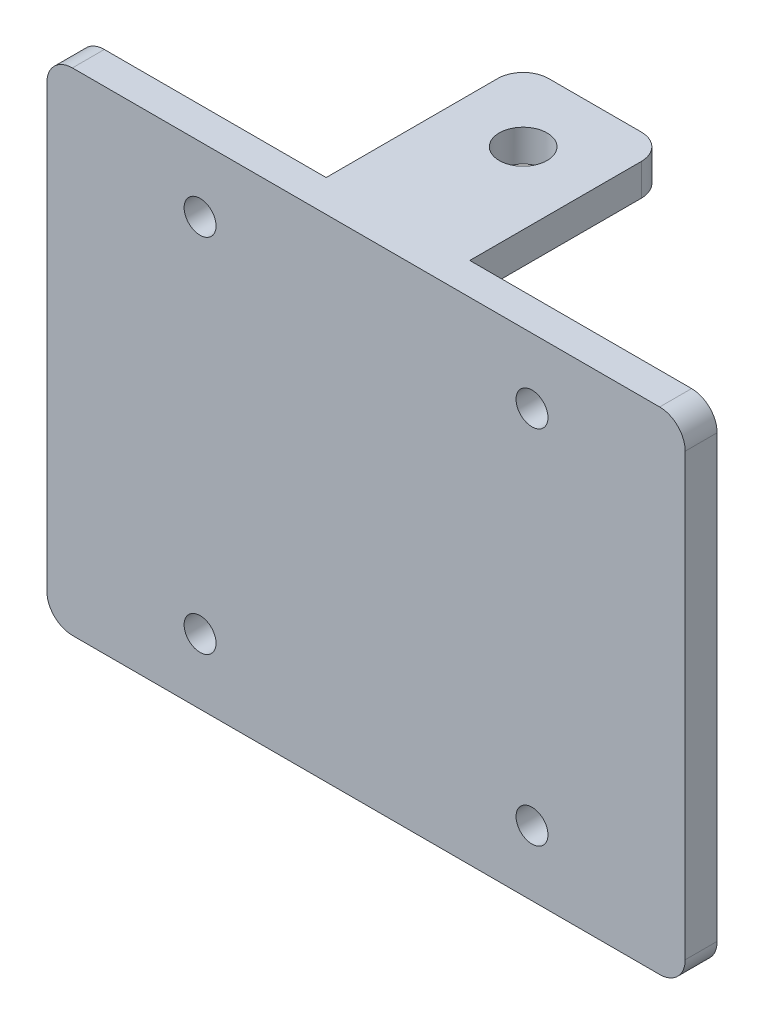
SolidWorks part; units mm, degrees
material "6061 Alloy"
ref_plane "Front Plane" through (0, 0, 0) normal (0, 0, 1) x (1, 0, 0)
ref_plane "Top Plane" through (0, 0, 0) normal (0, 1, 0) x (1, 0, 0)
ref_plane "Right Plane" through (0, 0, 0) normal (1, 0, 0) x (0, 0, -1)
sketch "Sketch1" plane through (0, 0, 0) normal (0, 0, 1) x (1, 0, 0)
  line L1 (0, 0) -> (63.5, 0)
  line L2 (0, 0) -> (0, 48.895)
  line L3 (0, 48.895) -> (63.5, 48.895)
  line L4 (63.5, 0) -> (63.5, 48.895)
  dimension "D1" = 63.5
  dimension "D2" = 48.895
extrude "Boss-Extrude1" add sketch "Sketch1" along normal blind 3.175
sketch "Sketch6" plane through (0, 48.895, 0) normal (0, 1, 0) x (1, 0, 0)
  line L0 (24.6062, 0) -> (24.6062, 19.5981)
  line L1 (63.5, 0) -> (0, 0) construction
  line L2 (24.6062, 19.5981) -> (38.8938, 19.5981)
  line L3 (38.8938, 19.5981) -> (38.8938, 0)
  line L4 (31.75, 19.5981) -> (31.75, 0) construction
  line L5 (24.6062, 0) -> (38.8938, 0)
  point P9 (31.75, 0)
  dimension "D1" = 14.2875
  dimension "D2" = 19.5981
extrude "Boss-Extrude3" add sketch "Sketch6" against normal blind 3.175
sketch "Sketch7" plane through (0, 48.895, 0) normal (0, 1, 0) x (1, 0, 0)
  line L0 (31.75, 19.5981) -> (31.75, 1.4238) construction
  line L1 (38.8938, 19.5981) -> (24.6062, 19.5981) construction
  circle A0 centre (31.75, 12.4544) radius 2.3812
  point P4 (31.75, 14.8356)
  point P8 (31.75, 19.5981)
  dimension "D1" = 4.7625
  dimension "D2" = 4.7625
extrude "Cut-Extrude2" cut sketch "Sketch7" against normal up to next
sketch "Sketch4" plane through (0, 0, 3.175) normal (0, 0, 1) x (1, 0, 0)
  line L0 (0, 0) -> (63.5, 0) construction
  line L1 (0, 48.895) -> (0, 0) construction
  line L2 (63.5, 24.4475) -> (0, 24.4475) construction
  line L3 (63.5, 0) -> (63.5, 48.895) construction
  line L4 (31.75, 0) -> (31.75, 48.895) construction
  line L5 (63.5, 48.895) -> (0, 48.895) construction
  circle A0 centre (15.24, 6.477) radius 1.5875
  circle A1 centre (15.24, 42.418) radius 1.5875
  circle A2 centre (48.26, 42.418) radius 1.5875
  circle A3 centre (48.26, 6.477) radius 1.5875
  dimension "D1" = 3.175
  dimension "D2" = 6.477
  dimension "D3" = 15.24
extrude "Cut-Extrude1" cut sketch "Sketch4" against normal up to next from surface starting at face at (31.75, 24.4475, 3.175)
fillet "Fillet1" radius 2.54 6 edges at (0, 0, 1.5875) (63.5, 0, 1.5875) (0, 48.895, 1.5875) (63.5, 48.895, 1.5875) (24.6062, 47.3075, -19.5981) (38.8938, 47.3075, -19.5981)
sketch "Sketch2" plane through (0, 0, 3.175) normal (0, 0, 1) x (1, 0, 0)
  line L0 (31.75, 0) -> (31.75, 48.895)
  line L1 (2.54, 0) -> (60.96, 0) construction
  line L2 (60.96, 48.895) -> (2.54, 48.895) construction
  line L3 (63.5, 24.4475) -> (0, 24.4475)
  line L4 (63.5, 2.54) -> (63.5, 46.355) construction
  line L5 (0, 46.355) -> (0, 2.54) construction
sketch "Sketch3" plane through (0, 0, 0) normal (0, 0, -1) x (-1, 0, 0)
  line L0 (0, 24.4475) -> (-63.5, 24.4475)
  line L1 (0, 46.355) -> (0, 2.54) construction
  line L2 (-63.5, 2.54) -> (-63.5, 46.355) construction
  line L3 (-31.75, 0) -> (-31.75, 48.895)
  line L4 (-2.54, 0) -> (-60.96, 0) construction
  line L6 (-29.3688, 48.895) -> (-34.1313, 48.895) construction
  point P10 (0, 0)
